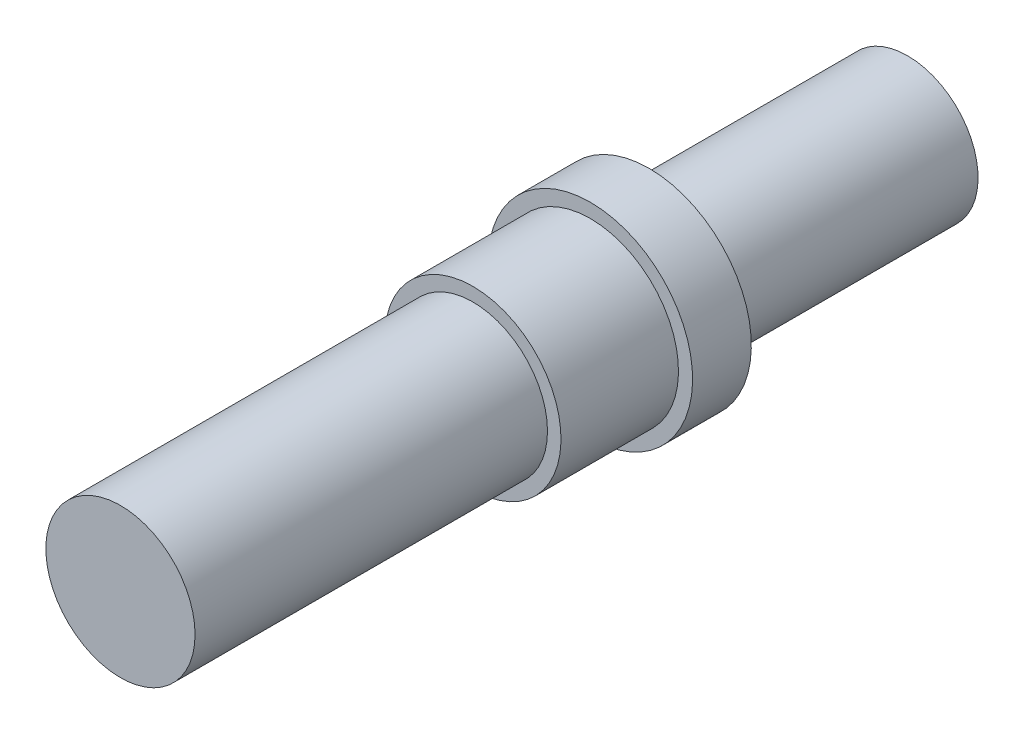
SolidWorks part; units mm, degrees
ref_plane "Front Plane" through (0, 0, 0) normal (0, 0, 1) x (1, 0, 0)
ref_plane "Top Plane" through (0, 0, 0) normal (0, 1, 0) x (1, 0, 0)
ref_plane "Right Plane" through (0, 0, 0) normal (1, 0, 0) x (0, 0, -1)
sketch "Sketch3" plane through (0, 0, 0) normal (1, 0, 0) x (0, 0, -1)
  line L1 (9.9982, 8.7) -> (14.9982, 8.7)
  line L2 (14.9982, 8.7) -> (14.9982, 6)
  line L3 (14.9982, 6) -> (34.9982, 6)
  line L4 (34.9982, 6) -> (34.9982, 0)
  line L5 (34.9982, 0) -> (0, 0)
  line L6 (9.9982, 7.5) -> (-0.0018, 7.5)
  line L7 (-0.0018, 7.5) -> (-0.0018, 0)
  line L8 (-0.0018, 0) -> (0, 0)
  line L9 (9.9982, 7.5) -> (9.9982, 8.7)
  point P2 (0, 0)
  point P10 (0, 0)
  point P11 (3.3903, 0)
  point P12 (0, 0)
  point P13 (0, 0)
  point P14 (0, 0)
  dimension "D1" = 8.7
  dimension "D2" = 6
  dimension "D3" = 20
  dimension "D4" = 5
  dimension "D5" = 10
  dimension "D6" = 7.5
revolve "Initial Resolve -- Exact Length" add sketch "Sketch3" angle 360 about L5
sketch "Sketch5" plane through (0, 0, 0.0018) normal (0, 0, 1) x (1, 0, 0)
  circle A2 centre (0, 0) radius 6.35
  dimension "D1" = 12.7
extrude "Outside Extrude" add sketch "Sketch5" along normal blind 30
sketch "Sketch6" plane through (0, 0, -34.9982) normal (0, 0, -1) x (-1, 0, 0)
  circle A2 centre (0, 0) radius 6
  circle A3 centre (0, 0) radius 6
  dimension "D1" = 0
extrude "Inside Extrude" add sketch "Sketch6" along normal blind 2
